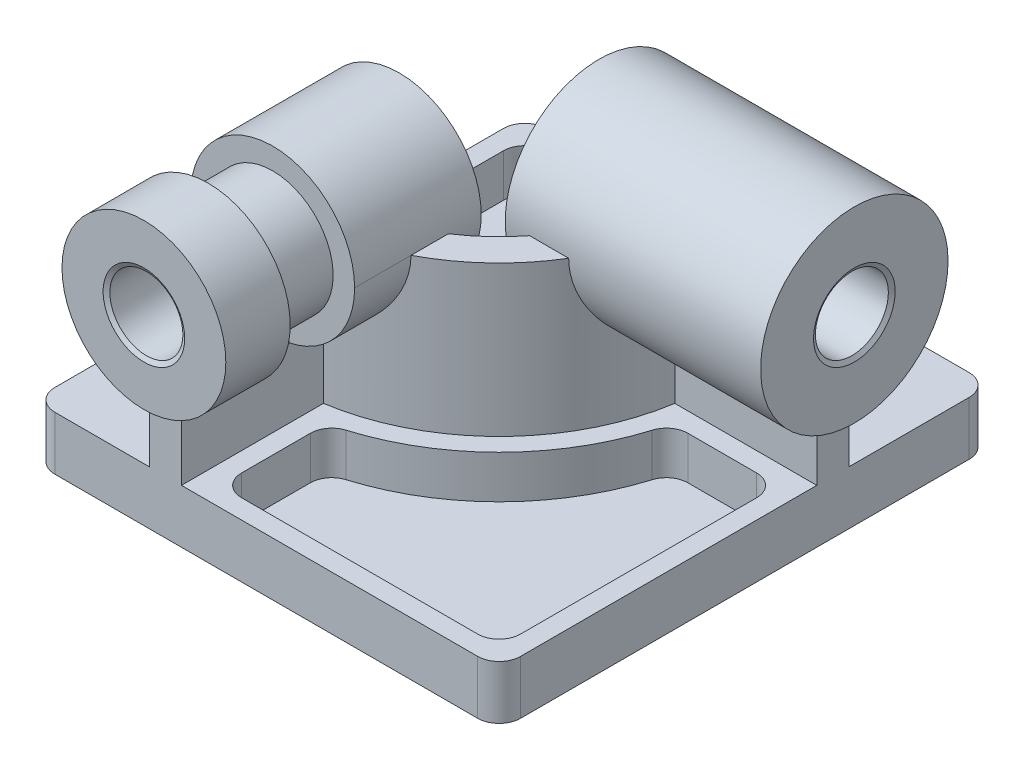
SolidWorks part; units mm, degrees
material "Alloy Steel"
ref_plane "Front Plane" through (0, 0, 0) normal (0, 0, 1) x (1, 0, 0)
ref_plane "Top Plane" through (0, 0, 0) normal (0, 1, 0) x (1, 0, 0)
ref_plane "Right Plane" through (0, 0, 0) normal (1, 0, 0) x (0, 0, -1)
sketch "Sketch1" plane through (0, 0, 0) normal (0, 1, 0) x (1, 0, 0)
  line L1 (-54, 66) -> (163, 66)
  line L2 (-54, 66) -> (-54, -163)
  line L3 (-54, -163) -> (163, -163)
  line L4 (163, 66) -> (163, -163)
  dimension "D1" = 229
  dimension "D2" = 217
  dimension "D3" = 163
  dimension "D4" = 163
extrude "Boss-Extrude1" add sketch "Sketch1" along normal blind 25
sketch "Sketch2" plane through (0, 25, 0) normal (0, 1, 0) x (1, 0, 0)
  line L0 (-54, -163) -> (163, -163) construction
  line L1 (0, -163) -> (15, -163)
  line L2 (0, -163) -> (0, -83)
  line L3 (0, -83) -> (15, -83)
  line L4 (15, -163) -> (15, -83)
  line L5 (163, -163) -> (163, 66) construction
  line L6 (163, 0) -> (83, 0)
  line L7 (163, 0) -> (163, -15)
  line L8 (163, -15) -> (83, -15)
  line L9 (83, 0) -> (83, -15)
  arc A0 (0, -83) -> (83, 0) centre (0, 0) ccw
  arc A1 (0, -98) -> (98, 0) centre (0, 0) ccw
  line M6 (-54, -163) -> (163, -163)
  line M7 (163, -163) -> (163, 66)
  dimension "D1" = 15
  dimension "D2" = 80
  dimension "D3" = 15
  dimension "D4" = 80
  dimension "D5" = 15
extrude "Boss-Extrude2" add sketch "Sketch2" along normal blind 70 contours A1 L2 L4 M6 | L2 A1 L4 L3 | L4 A1 L8 L9 A0 L3 | L8 A1 L6 L9 | A1 L8 L6 M7 region at (7.5221, 25, 130.3071) region at (7.4014, 25, 90.312) region at (60.0471, 25, 60.0471) region at (130.3071, 25, 7.5221) region at (90.312, 25, 7.4014)
sketch "Sketch3" plane through (0, 0, 163) normal (0, 0, 1) x (1, 0, 0)
  line L0 (0, 95) -> (15, 95) construction
  circle A0 centre (7.5, 95) radius 38.1667
  point P4 (7.5, 95)
  dimension "D1" = 76.3333
extrude "Boss-Extrude3" add sketch "Sketch3" against normal blind 119 from offset 10
ref_plane "Plane1" through (7.5, 0, 0) normal (-1, 0, 0) x (0, 0, 1)
sketch "Sketch11" plane through (7.5, 0, 0) normal (-1, 0, 0) x (0, 0, 1)
  line L0 (173, 133.1667) -> (54, 133.1667) construction
  line L1 (113, 133.1667) -> (143, 133.1667)
  line L2 (113, 133.1667) -> (113, 123.1667)
  line L3 (113, 123.1667) -> (143, 123.1667)
  line L4 (143, 133.1667) -> (143, 123.1667)
  dimension "D1" = 10
  dimension "D2" = 30
  dimension "D3" = 30
revolve "Cut-Revolve7" cut sketch "Sketch11" angle 360 about axis through (7.5, 95, 54) along (0, 0, 1) region at (7.5, 128.1667, 128)
extrude "Boss-Extrude6" add sketch "Sketch2<3>" along normal up to surface (70 mm away) contours A1 L2 L4 M6 region at (7.5221, 25, 130.3071) up to face at (102.4051, 95, 32.8)
sketch "Sketch2<3>" plane through (0, 25, 0) normal (0, 1, 0) x (1, 0, 0) same geometry as "Sketch2"
sketch "Sketch4" plane through (163, 0, 0) normal (1, 0, 0) x (0, 0, -1)
  line L0 (-15, 95) -> (0, 95) construction
  circle A0 centre (-7.5, 95) radius 43.6667
  dimension "D1" = 87.3333
extrude "Boss-Extrude4" add sketch "Sketch4" against normal blind 119 from offset 10
sketch "Sketch5" plane through (173, 0, 0) normal (1, 0, 0) x (0, 0, -1)
  circle A0 centre (-7.5, 95) radius 17
  dimension "D1" = 34
extrude "Cut-Extrude1" cut sketch "Sketch5" against normal through all
sketch "Sketch6" plane through (0, 0, 173) normal (0, 0, 1) x (1, 0, 0)
  circle A0 centre (7.5, 95) radius 17
  dimension "D1" = 34
extrude "Cut-Extrude2" cut sketch "Sketch6" against normal through all
sketch "Sketch8" plane through (0, 25, 0) normal (0, 1, 0) x (1, 0, 0)
  line L14 (24, -104.2737) -> (24, -154)
  line L15 (24, -154) -> (154, -154)
  line L16 (154, -154) -> (154, -24)
  line L17 (154, -24) -> (104.2737, -24)
  line L24 (24, -111.9509) -> (24, -144)
  line L25 (34, -154) -> (144, -154)
  line L26 (154, -144) -> (154, -34)
  line L27 (144, -24) -> (111.9509, -24)
  arc A5 (24, -111.9509) -> (31.094, -102.3824) centre (34, -111.9509) cw
  arc A12 (24, -104.2737) -> (104.2737, -24) centre (0, 0) ccw
  arc A13 (31.094, -102.3824) -> (102.3824, -31.094) centre (0, 0) ccw
  arc A14 (24, -144) -> (34, -154) centre (34, -144) ccw
  arc A15 (144, -154) -> (154, -144) centre (144, -144) ccw
  arc A16 (154, -34) -> (144, -24) centre (144, -34) ccw
  arc A17 (111.9509, -24) -> (102.3824, -31.094) centre (111.9509, -34) ccw
  dimension "D2" = 10
  dimension "D1" = 9
extrude "Cut-Extrude3" cut sketch "Sketch8" against normal offset from surface (20 mm away) 5 up to face at (54.5, 0, 48.5)
fillet "Fillet1" radius 10 4 edges at (163, 12.5, -66) (-54, 12.5, -66) (-54, 12.5, 163) (163, 12.5, 163)
chamfer "Chamfer1" distance 2 angle 30 4 edges at (24.5, 95, 173) (24.5, 95, 54) (54, 95, -9.5) (173, 95, -9.5) first distance on face at (24.5, 95, 173) first distance on face at (173, 95, -9.5)
sketch "Sketch10" plane through (0, 25, 0) normal (0, 1, 0) x (1, 0, 0)
  line L6 (74, 0) -> (74, 47)
  line L7 (64, 57) -> (-35, 57)
  line L8 (-45, 47) -> (-45, -64)
  line L9 (-35, -74) -> (0, -74)
  line L10 (153, 66) -> (-44, 66) construction
  line L11 (-54, 56) -> (-54, -153) construction
  arc A5 (-45, -64) -> (-35, -74) centre (-35, -64) ccw
  arc A6 (0, -74) -> (74, 0) centre (0, 0) ccw
  arc A7 (0, -74) -> (74, 0) centre (0, 0) ccw
  arc A8 (-35, 57) -> (-45, 47) centre (-35, 47) ccw
  arc A9 (74, 47) -> (64, 57) centre (64, 47) ccw
  dimension "D4" = 10
  dimension "D2" = 9
  dimension "D3" = 9
  dimension "D1" = 9
extrude "Cut-Extrude4" cut sketch "Sketch10" against normal offset from surface (20 mm away) 5 up to face at (54.5, 0, 48.5)
equation "\"A\" = 229"
equation "\"B\" = 217"
equation "\"C\" = 163"
equation "\"D\" = 119"
equation "\"E\" = 34"
equation "\"X\"= \"A\" / 3"
equation "\"Y\"= \"B\" / 3 + 15"
equation "\"D1@Sketch1\"=\"A\""
equation "\"D2@Sketch1\"=\"B\""
equation "\"D3@Sketch1\"=\"C\""
equation "\"D4@Sketch1\"=\"C\""
equation "\"D1@Sketch3\"=\"X\""
equation "\"D1@Boss-Extrude3\"=\"D\""
equation "\"D1@Sketch4\"=\"Y\""
equation "\"D1@Boss-Extrude4\"=\"D\""
equation "\"D1@Sketch5\"=\"E\""
equation "\"D1@Sketch6\"=\"E\""
